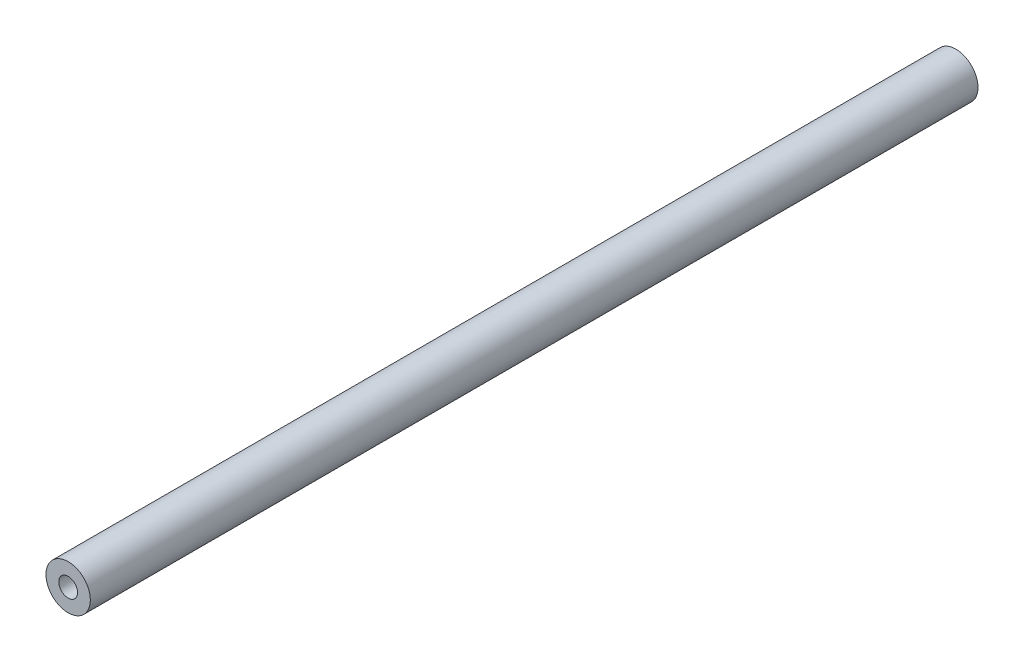
SolidWorks part; units mm, degrees
material "7075-T6, Plate (SS)"
ref_plane "Front Plane" through (0, 0, 0) normal (0, 0, 1) x (1, 0, 0)
ref_plane "Top Plane" through (0, 0, 0) normal (0, 1, 0) x (1, 0, 0)
ref_plane "Right Plane" through (0, 0, 0) normal (1, 0, 0) x (0, 0, -1)
sketch "Sketch1" plane through (0, 0, 0) normal (0, 0, 1) x (1, 0, 0)
  circle A1 centre (0, 0) radius 4.7625
  dimension "D1" = 9.525
extrude "Boss-Extrude1" add sketch "Sketch1" against normal blind 190.5
sketch "Sketch5" plane through (0, 0, -190.5) normal (0, 0, -1) x (-1, 0, 0)
  point P0 (0, 0)
hole_wizard "#10-32 Tapped Hole1" positions "Sketch5" profile "Sketch6" tap size "#10-32" standard "ANSI Inch"
sketch "Sketch6" plane through (0, 0, -190.5) normal (1, 0, 0) x (0, 1, 0)
  line L0 (0, 0) -> (0, 20.2633)
  line L1 (0, 20.2633) -> (2.0193, 19.05)
  line L2 (2.0193, 19.05) -> (2.0193, 0)
  line L5 (2.0193, 0) -> (0, 0)
  line L10 (0, 20.2633) -> (-2.0193, 19.05) construction
  line L11 (0, -6.35) -> (0, 107.95) construction
  dimension "Tap Drill Dia." = 4.0386
  dimension "Tap Drill Depth" = 19.05
  dimension "Drill Angle" = 118
cosmetic thread "Hole Thread1" parameters "D1"=9.652, "D2"=4.826
hole_wizard "#10-32 Tapped Hole4" positions "Sketch11" profile "Sketch12" tap size "#10-32" standard "ANSI Inch"
sketch "Sketch11" plane through (0, 0, 0) normal (0, 0, 1) x (1, 0, 0)
  point P0 (0, 0)
sketch "Sketch12" plane through (0, 0, 0) normal (1, 0, 0) x (0, -1, 0)
  line L0 (0, 0) -> (0, 20.2633)
  line L1 (0, 20.2633) -> (2.0193, 19.05)
  line L2 (2.0193, 19.05) -> (2.0193, 0)
  line L5 (2.0193, 0) -> (0, 0)
  line L10 (0, 20.2633) -> (-2.0193, 19.05) construction
  line L11 (0, -6.35) -> (0, 107.95) construction
  dimension "Tap Drill Dia." = 4.0386
  dimension "Tap Drill Depth" = 19.05
  dimension "Drill Angle" = 118
cosmetic thread "Hole Thread4" parameters "D1"=9.652, "D2"=4.826
